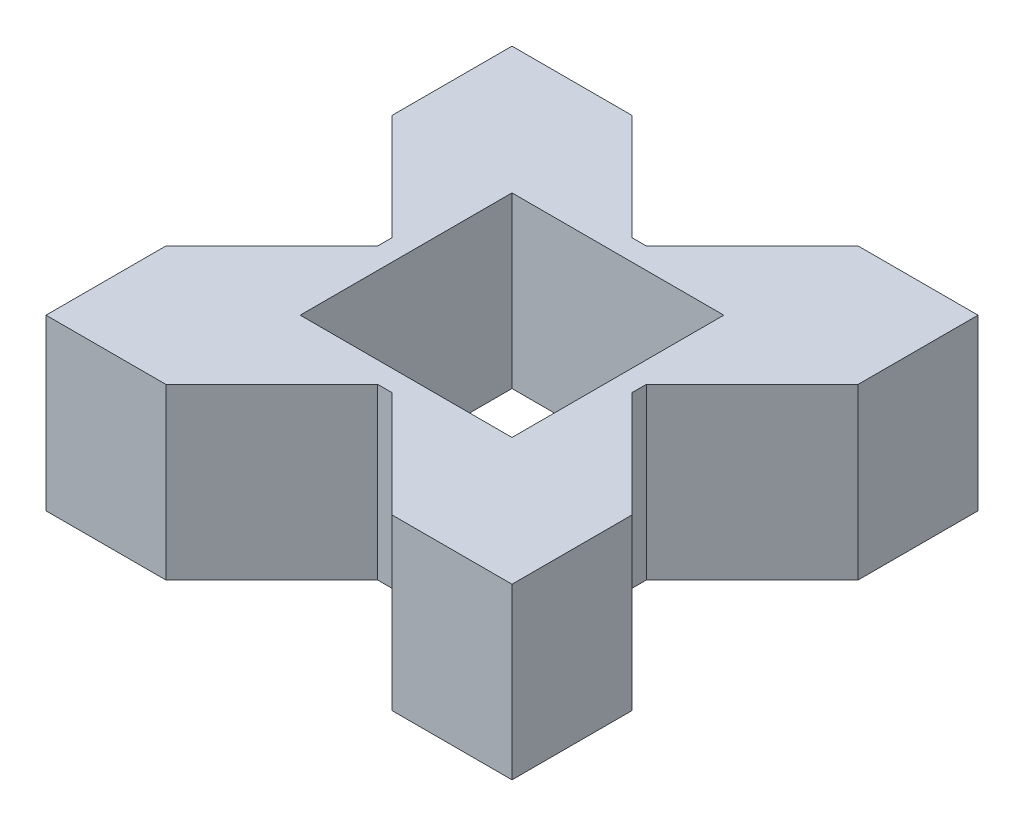
SolidWorks part; units mm, degrees
ref_plane "Front Plane" through (0, 0, 0) normal (0, 0, 1) x (1, 0, 0)
ref_plane "Top Plane" through (0, 0, 0) normal (0, 1, 0) x (1, 0, 0)
ref_plane "Right Plane" through (0, 0, 0) normal (1, 0, 0) x (0, 0, -1)
sketch "Sketch1" plane through (0, 0, 0) normal (0, 1, 0) x (1, 0, 0)
  line L0 (27.5, -13.3579) -> (-13.3579, 27.5)
  line L1 (27.5, -27.5) -> (-27.5, -27.5)
  line L2 (27.5, -27.5) -> (27.5, 27.5)
  line L3 (27.5, 27.5) -> (-27.5, 27.5)
  line L4 (-27.5, -27.5) -> (-27.5, 27.5)
  line L5 (27.5, -27.5) -> (-27.5, 27.5) construction
  line L6 (27.5, 27.5) -> (-27.5, -27.5) construction
  line L7 (13.3579, 27.5) -> (-27.5, -13.3579)
  line L8 (13.3579, -27.5) -> (-27.5, 13.3579)
  line L9 (27.5, 13.3579) -> (-13.3579, -27.5)
  line L10 (34.5711, 20.4289) -> (-20.4289, -34.5711) construction
  line L11 (20.4289, 34.5711) -> (-34.5711, -20.4289) construction
  line L12 (20.4289, -34.5711) -> (-34.5711, 20.4289) construction
  line L13 (34.5711, -20.4289) -> (-20.4289, 34.5711) construction
  line L15 (-15, 15) -> (15, 15)
  line L16 (-15, 15) -> (-15, -15)
  line L17 (-15, -15) -> (15, -15)
  line L18 (15, 15) -> (15, -15)
  line L19 (-15, 15) -> (15, -15) construction
  line L20 (-15, -15) -> (15, 15) construction
  point P0 (0, 0)
  point P22 (0, 0)
  dimension "D1" = 55
  dimension "D2" = 55
  dimension "D5" = 30
  dimension "D6" = 30
  dimension "D3" = 10
  dimension "D4" = 10
extrude "Boss-Extrude1" add sketch "Sketch1" along normal blind 20 contours L8 L7 L0 L3 L4 | L9 L2 L3 L7 L0 | L9 L0 L7 L8 | L9 L8 L7 L4 L1 | L0 L9 L8 L1 L2 | L15 L0 L7 | L18 L15 L7 L0 L9 | L15 L16 L8 L7 L0 | L8 L16 L7 | L16 L17 L9 L8 L7 | L18 L0 L9 L8 L17 | L9 L17 L8 | L18 L9 L0 region at (17.7145, 0, 17.7145) region at (9.742, 0, 9.742) region at (14.714, 0, 0) region at (17.7145, 0, -17.7145) region at (0, 0, 0) region at (9.742, 0, -9.742) region at (-9.742, 0, -9.742) region at (0, 0, -14.714) region at (-9.742, 0, 9.742) region at (0, 0, 14.714) region at (-17.7145, 0, 17.7145) region at (-17.7145, 0, -17.7145) region at (-14.714, 0, 0)
sketch "Sketch2" plane through (0, 20, 0) normal (0, 1, 0) x (1, 0, 0)
  line L1 (-12.5, 12.5) -> (12.5, 12.5)
  line L2 (-12.5, 12.5) -> (-12.5, -12.5)
  line L3 (-12.5, -12.5) -> (12.5, -12.5)
  line L4 (12.5, 12.5) -> (12.5, -12.5)
  line L5 (-12.5, 12.5) -> (12.5, -12.5) construction
  line L6 (-12.5, -12.5) -> (12.5, 12.5) construction
  point P0 (0, 0)
  dimension "D1" = 25
  dimension "D2" = 25
extrude "Cut-Extrude2" cut sketch "Sketch2" against normal through all
